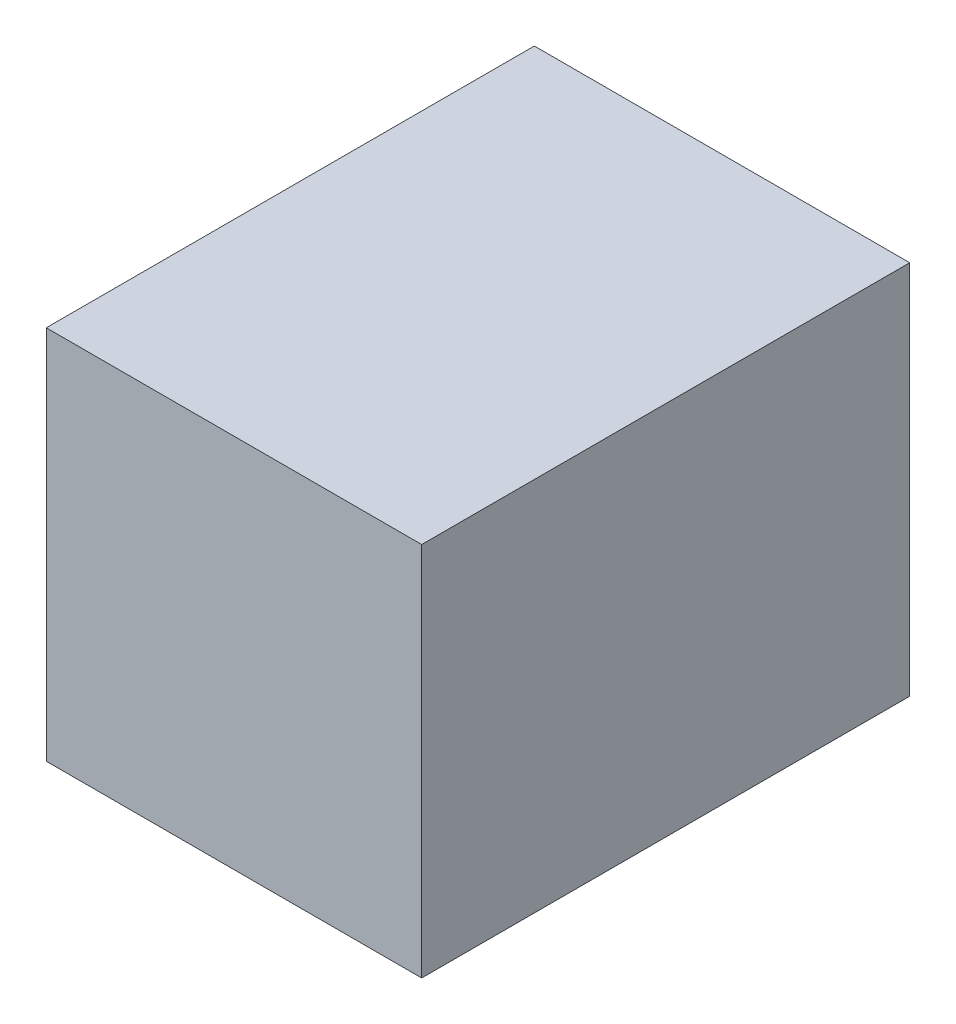
SolidWorks part; units mm, degrees
ref_plane "Front Plane" through (0, 0, 0) normal (0, 0, 1) x (1, 0, 0)
ref_plane "Top Plane" through (0, 0, 0) normal (0, 1, 0) x (1, 0, 0)
ref_plane "Right Plane" through (0, 0, 0) normal (1, 0, 0) x (0, 0, -1)
sketch "Sketch1" plane through (0, 0, 0) normal (0, 1, 0) x (1, 0, 0)
  line L1 (-5, -6.5) -> (5, -6.5)
  line L2 (-5, -6.5) -> (-5, 6.5)
  line L3 (-5, 6.5) -> (5, 6.5)
  line L4 (5, -6.5) -> (5, 6.5)
  line L5 (-5, -6.5) -> (5, 6.5) construction
  line L6 (-5, 6.5) -> (5, -6.5) construction
  point P0 (0, 0)
  dimension "D1" = 10
  dimension "D2" = 13
extrude "Boss-Extrude1" add sketch "Sketch1" along normal blind 10
sketch "Sketch2" plane through (-5, 0, 0) normal (-1, 0, 0) x (0, 0, 1)
  line L0 (-6.5, 0) -> (6.5, 0) construction
  line L1 (-4.25, 1.4) -> (4.25, 1.4)
  line L2 (-4.25, 1.4) -> (-4.25, 6.4)
  line L3 (-4.25, 6.4) -> (4.25, 6.4)
  line L4 (4.25, 1.4) -> (4.25, 6.4)
  point P6 (0, 1.4)
  dimension "D1" = 1.4
  dimension "D2" = 5
  dimension "D3" = 8.5
extrude "Cut-Extrude1" cut sketch "Sketch2" against normal blind 7.5
sketch "Sketch3" plane through (0, 0, -6.5) normal (0, 0, -1) x (-1, 0, 0)
  line L0 (-5, 10) -> (-5, 0) construction
  line L1 (-2.5, 1.4) -> (0.5, 1.4)
  line L2 (-2.5, 1.4) -> (-2.5, 6.4)
  line L3 (-2.5, 6.4) -> (0.5, 6.4)
  line L4 (0.5, 1.4) -> (0.5, 6.4)
  line L5 (-5, 0) -> (5, 0) construction
  dimension "D1" = 2.5
  dimension "D2" = 1.4
  dimension "D3" = 5
  dimension "D4" = 3
extrude "Cut-Extrude3" cut sketch "Sketch3" against normal up to surface (10.75 mm away) up to face at (-1.25, 3.9, 4.25)
fillet "Fillet3" radius 3 2 edges at (-1.25, 6.4, 4.25) (-2.75, 6.4, -4.25)
fillet "Fillet5" radius 1.5 4 edges at (2.5, 2.4, 4.25) (2.5, 5.5213, 3.3713) (2.5, 6.4, -2.625) (-0.5, 6.4, -3.875)
